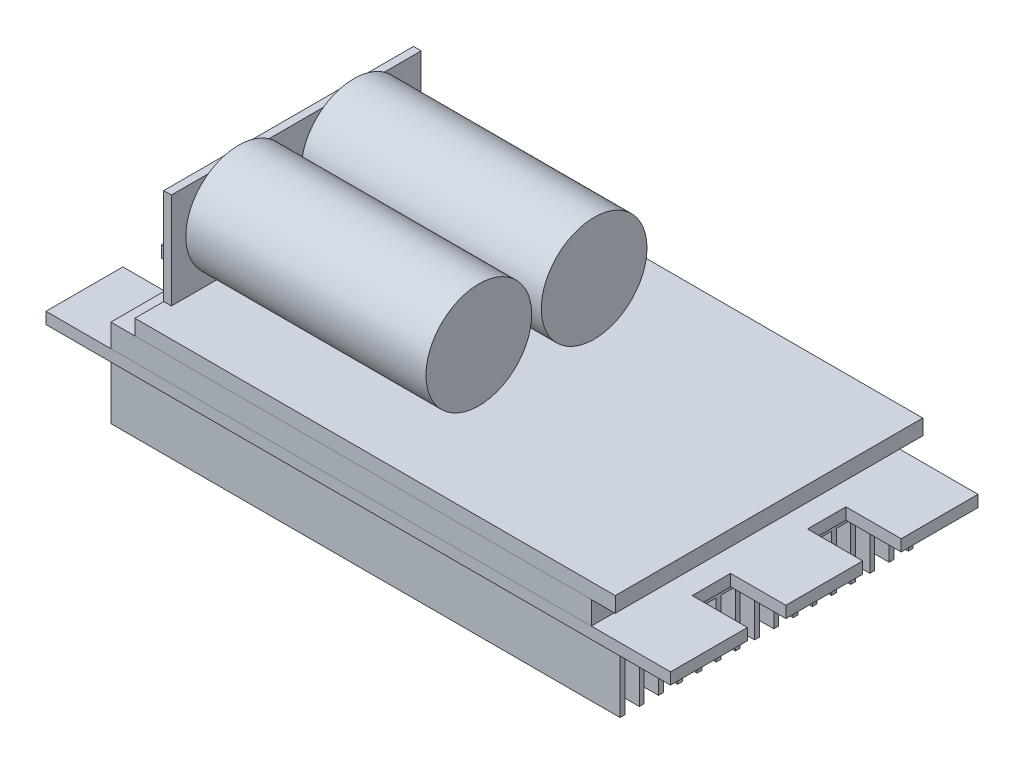
SolidWorks part; units mm, degrees
material "Copper"
ref_plane "Front Plane" through (0, 0, 0) normal (0, 0, 1) x (1, 0, 0)
ref_plane "Top Plane" through (0, 0, 0) normal (0, 1, 0) x (1, 0, 0)
ref_plane "Right Plane" through (0, 0, 0) normal (1, 0, 0) x (0, 0, -1)
sketch "Sketch1" plane through (0, 0, 0) normal (0, 1, 0) x (1, 0, 0)
  line L0 (-26.75, 16) -> (-32.5, 16)
  line L1 (-26.75, -16) -> (26.75, -16)
  line L2 (-26.75, -16) -> (-26.75, 16) construction
  line L3 (-26.75, 16) -> (26.75, 16)
  line L4 (26.75, -16) -> (26.75, 16) construction
  line L5 (-26.75, -16) -> (26.75, 16) construction
  line L6 (-26.75, 16) -> (26.75, -16) construction
  line L7 (-32.5, 16) -> (-32.5, 8)
  line L8 (-32.5, 8) -> (-26.75, 8)
  line L9 (-26.75, 4) -> (-32.5, 4)
  line L10 (-32.5, 4) -> (-32.5, -4)
  line L11 (-32.5, -4) -> (-26.75, -4)
  line L12 (-26.75, -16) -> (-32.5, -16)
  line L13 (-32.5, -16) -> (-32.5, -8)
  line L14 (-32.5, -8) -> (-26.75, -8)
  line L15 (0, 0) -> (-32.5, 0) construction
  line L16 (26.75, 16) -> (32.5, 16)
  line L17 (32.5, 16) -> (32.5, 8)
  line L18 (32.5, 8) -> (26.75, 8)
  line L19 (26.75, -16) -> (32.5, -16)
  line L20 (32.5, -16) -> (32.5, -8)
  line L21 (32.5, -8) -> (26.75, -8)
  line L22 (26.75, 4) -> (32.5, 4)
  line L23 (32.5, 4) -> (32.5, -4)
  line L24 (32.5, -4) -> (26.75, -4)
  line L25 (0, 0) -> (32.5, 0) construction
  line L26 (-26.75, 8) -> (-26.75, 4)
  line L27 (-26.75, -4) -> (-26.75, -8)
  line L28 (26.75, 8) -> (26.75, 4)
  line L29 (26.75, -4) -> (26.75, -8)
  point P0 (0, 0)
  dimension "D1" = 53.5
  dimension "D2" = 32
  dimension "D3" = 65
  dimension "D4" = 8
extrude "Boss-Extrude1" add sketch "Sketch1" along normal blind 1.2
sketch "Sketch2" plane through (0, 1.2, 0) normal (0, 1, 0) x (1, 0, 0)
  line L0 (32.5, 16) -> (-32.5, 16) construction
  line L1 (-25.75, -16) -> (24.25, -16)
  line L2 (-25.75, -16) -> (-25.75, 16)
  line L3 (-25.75, 16) -> (24.25, 16)
  line L4 (24.25, -16) -> (24.25, 16)
  line L5 (-25.75, -16) -> (24.25, 16) construction
  line L6 (-25.75, 16) -> (24.25, -16) construction
  line L7 (-26.75, 8) -> (-26.75, 4) construction
  point P0 (-0.75, 0)
  dimension "D1" = 50
  dimension "D2" = 1
extrude "Boss-Extrude2" add sketch "Sketch2" along normal blind 2.4 separate body
sketch "Sketch3" plane through (0, 3.6, 0) normal (0, 1, 0) x (1, 0, 0)
  line L0 (32.5, 16) -> (-32.5, 16) construction
  line L1 (26.75, -16) -> (-23.25, -16)
  line L2 (26.75, -16) -> (26.75, 16)
  line L3 (26.75, 16) -> (-23.25, 16)
  line L4 (-23.25, -16) -> (-23.25, 16)
  line L5 (26.75, -16) -> (-23.25, 16) construction
  line L6 (26.75, 16) -> (-23.25, -16) construction
  line L7 (26.75, 4) -> (26.75, 8) construction
  point P0 (1.75, 0)
  dimension "D1" = 50
extrude "Boss-Extrude3" add sketch "Sketch3" along normal blind 1.6 separate body
sketch "Sketch4" plane through (0, 5.2, 0) normal (0, 1, 0) x (1, 0, 0)
  line L1 (-23.25, -13) -> (-22.45, -13)
  line L2 (-23.25, -13) -> (-23.25, 13)
  line L3 (-23.25, 13) -> (-22.45, 13)
  line L4 (-22.45, -13) -> (-22.45, 13)
  line L5 (-23.25, -13) -> (-22.45, 13) construction
  line L6 (-23.25, 13) -> (-22.45, -13) construction
  line L8 (-23.25, 16) -> (-23.25, -16) construction
  point P0 (-22.85, 0)
  dimension "D1" = 0.8
  dimension "D2" = 26
extrude "Boss-Extrude4" add sketch "Sketch4" along normal blind 10
sketch "Sketch5" plane through (-22.45, 0, 0) normal (1, 0, 0) x (0, 0, -1)
  line L0 (-16, 5.2) -> (16, 5.2) construction
  line L1 (6, 10.7) -> (-6, 10.7) construction
  line L2 (6, 10.7) -> (6, 5.2) construction
  line L3 (6, 5.2) -> (-6, 5.2) construction
  line L4 (-6, 10.7) -> (-6, 5.2) construction
  line L5 (6, 10.7) -> (-6, 5.2) construction
  line L6 (6, 5.2) -> (-6, 10.7) construction
  circle A0 centre (-6, 10.7) radius 5.5
  circle A1 centre (6, 10.7) radius 5.5
  point P0 (0, 7.95)
  dimension "D3" = 11
  dimension "D1" = 5.5
  dimension "D2" = 12
extrude "Boss-Extrude6" add sketch "Sketch5" along normal blind 25 separate body
sketch "Sketch6" plane through (0, 0, 0) normal (0, -1, 0) x (-1, 0, 0)
  line L5 (26.5, 15.25) -> (-26.5, 15.25)
  line L6 (26.5, 15.25) -> (26.5, -15.25)
  line L7 (26.5, -15.25) -> (-26.5, -15.25)
  line L8 (-26.5, 15.25) -> (-26.5, -15.25)
  line L9 (26.5, 15.25) -> (-26.5, -15.25) construction
  line L10 (26.5, -15.25) -> (-26.5, 15.25) construction
  point P0 (0, 0)
  point P1 (0, 0)
  dimension "D1" = 53
  dimension "D2" = 30.5
extrude "Boss-Extrude7" add sketch "Sketch6" along normal blind 6.3
sketch "Sketch8" plane through (26.5, 0, 0) normal (1, 0, 0) x (0, 0, -1)
  line L0 (-15.25, 0) -> (-15.25, -6.3)
  line L1 (-15.25, -6.3) -> (-14.75, -6.3)
  line L2 (15.25, -6.3) -> (-15.25, -6.3) construction
  line L3 (-14.75, -6.3) -> (-14.75, -0.5)
  line L5 (15.25, 0) -> (15.25, -6.3)
  line L6 (15.25, -6.3) -> (14.75, -6.3)
  line L8 (-15.25, 0) -> (-23.6125, 0)
  line L9 (-23.6125, 0) -> (-23.6125, -15.9473)
  line L10 (-23.6125, -15.9473) -> (23.6125, -15.9473)
  line L11 (23.6125, -15.9473) -> (23.6125, 0)
  line L12 (23.6125, 0) -> (15.25, 0)
  line L13 (-14.75, -0.5) -> (-13.25, -0.5)
  line L14 (-13.25, -0.5) -> (-13.25, -6.3)
  line L15 (-13.25, -6.3) -> (-12.75, -6.3)
  line L16 (-12.75, -6.3) -> (-12.75, -0.5)
  line L18 (-12.75, -0.5) -> (-11.25, -0.5)
  line L19 (-11.25, -0.5) -> (-11.25, -6.3)
  line L20 (-11.25, -6.3) -> (-10.75, -6.3)
  line L21 (-10.75, -6.3) -> (-10.75, -0.5)
  line L22 (-10.75, -0.5) -> (-9.25, -0.5)
  line L23 (-9.25, -0.5) -> (-9.25, -6.3)
  line L24 (-9.25, -6.3) -> (-8.75, -6.3)
  line L25 (-8.75, -6.3) -> (-8.75, -0.5)
  line L26 (-8.75, -0.5) -> (-7.25, -0.5)
  line L27 (-7.25, -0.5) -> (-7.25, -6.3)
  line L28 (-7.25, -6.3) -> (-6.75, -6.3)
  line L29 (-6.75, -6.3) -> (-6.75, -0.5)
  line L30 (-6.75, -0.5) -> (-5.25, -0.5)
  line L31 (-5.25, -0.5) -> (-5.25, -6.3)
  line L32 (-5.25, -6.3) -> (-4.75, -6.3)
  line L33 (-4.75, -6.3) -> (-4.75, -0.5)
  line L34 (-4.75, -0.5) -> (-3.25, -0.5)
  line L35 (-3.25, -0.5) -> (-3.25, -6.3)
  line L36 (-3.25, -6.3) -> (-2.75, -6.3)
  line L37 (-2.75, -6.3) -> (-2.75, -0.5)
  line L38 (-2.75, -0.5) -> (-1.25, -0.5)
  line L39 (-1.25, -0.5) -> (-1.25, -6.3)
  line L40 (-1.25, -6.3) -> (-0.75, -6.3)
  line L41 (-0.75, -6.3) -> (-0.75, -0.5)
  line L42 (-0.75, -0.5) -> (0.75, -0.5)
  line L43 (0.75, -0.5) -> (0.75, -6.3)
  line L44 (0.75, -6.3) -> (1.25, -6.3)
  line L45 (1.25, -6.3) -> (1.25, -0.5)
  line L46 (1.25, -0.5) -> (2.75, -0.5)
  line L47 (2.75, -0.5) -> (2.75, -6.3)
  line L48 (2.75, -6.3) -> (3.25, -6.3)
  line L49 (3.25, -6.3) -> (3.25, -0.5)
  line L50 (3.25, -0.5) -> (4.75, -0.5)
  line L51 (4.75, -0.5) -> (4.75, -6.3)
  line L52 (4.75, -6.3) -> (5.25, -6.3)
  line L53 (5.25, -6.3) -> (5.25, -0.5)
  line L54 (5.25, -0.5) -> (6.75, -0.5)
  line L55 (6.75, -0.5) -> (6.75, -6.3)
  line L56 (6.75, -6.3) -> (7.25, -6.3)
  line L57 (7.25, -6.3) -> (7.25, -0.5)
  line L58 (7.25, -0.5) -> (8.75, -0.5)
  line L59 (8.75, -0.5) -> (8.75, -6.3)
  line L60 (8.75, -6.3) -> (9.25, -6.3)
  line L61 (9.25, -6.3) -> (9.25, -0.5)
  line L62 (9.25, -0.5) -> (10.75, -0.5)
  line L63 (10.75, -0.5) -> (10.75, -6.3)
  line L64 (10.75, -6.3) -> (11.25, -6.3)
  line L65 (11.25, -6.3) -> (11.25, -0.5)
  line L66 (11.25, -0.5) -> (12.75, -0.5)
  line L67 (12.75, -0.5) -> (12.75, -6.3)
  line L68 (12.75, -6.3) -> (13.25, -6.3)
  line L69 (13.25, -6.3) -> (13.25, -0.5)
  line L70 (13.25, -0.5) -> (14.75, -0.5)
  line L71 (14.75, -0.5) -> (14.75, -6.3)
  line L72 (14.75, -6.3) -> (15.25, -6.3)
  line L73 (15.25, -6.3) -> (15.25, -0.5)
  line M7 (-15.25, 0) -> (-15.25, -6.3)
  line M8 (-15.25, -6.3) -> (15.25, -6.3)
  line M9 (15.25, -6.3) -> (15.25, 0)
  dimension "D1" = 0.5
  dimension "D2" = 5.8
  dimension "D3" = 2
  dimension "D4" = 0.5
  dimension "D5" = 15
extrude "Cut-Extrude7" cut sketch "Sketch8" against normal through all contours L11 L12 L5 L8 L9 L10 M9 M8 M7 | L14 L13 L3 M8 | L19 L18 L16 M8 | L23 L22 L21 M8 | L27 L26 L25 M8 | L31 L30 L29 M8 | L35 L34 L33 M8 | L39 L38 L37 M8 | L43 L42 L41 M8 | L47 L46 L45 M8 | L51 L50 L49 M8 | L55 L54 L53 M8 | L59 L58 L57 M8 | L63 L62 L61 M8 | L67 L66 L65 M8 | L71 L70 L69 M8 | L73 L72 L71 L70 L69 L68 L67 L66 L65 L64 L63 L62 L61 L60 L59 L58 L57 L56 L55 L54 L53 L52 L51 L50 L49 L48 L47 L46 L45 L44 L43 L42 L41 L40 L39 L38 L37 L36 L35 L34 L33 L32 L31 L30 L29 L28 L27 L26 L25 L24 L23 L22 L21 L20 L19 L18 L16 L15 L14 L13 L3 L1 L0 L8 L9 L10 L11 L12 L5 L6 region at (26.5, -9.6259, 0) region at (26.5, -3.4, 14) region at (26.5, -3.4, 12) region at (26.5, -3.4, 10) region at (26.5, -3.4, 8) region at (26.5, -3.4, -14) region at (26.5, -3.4, 6) region at (26.5, -3.4, -12) region at (26.5, -3.4, 4) region at (26.5, -3.4, -10) region at (26.5, -3.4, 2) region at (26.5, -3.4, -8) region at (26.5, -3.4, 0) region at (26.5, -3.4, -6) region at (26.5, -3.4, -2) region at (26.5, -3.4, -4)
